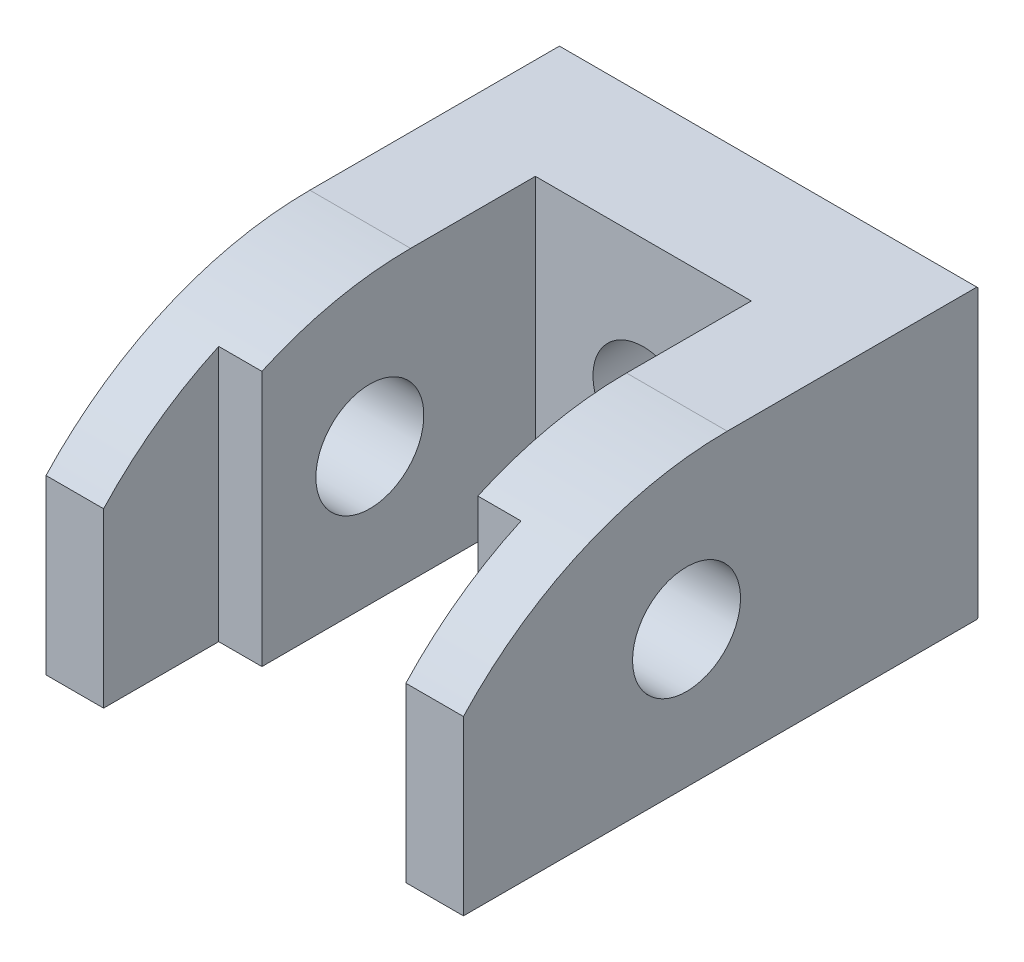
SolidWorks part; units mm, degrees
material "1060 Alloy"
ref_plane "Front Plane" through (0, 0, 0) normal (0, 0, 1) x (1, 0, 0)
ref_plane "Top Plane" through (0, 0, 0) normal (0, 1, 0) x (1, 0, 0)
ref_plane "Right Plane" through (0, 0, 0) normal (1, 0, 0) x (0, 0, -1)
sketch "Sketch2" plane through (0, 0, 0) normal (1, 0, 0) x (0, 0, -1)
  line L0 (0, 0) -> (0, 24)
  line L1 (0, 0) -> (65, 0)
  line L2 (65, 0) -> (80, 8.6603)
  line L3 (80, 8.6603) -> (80, 31.3397)
  line L4 (80, 31.3397) -> (65, 40)
  line L5 (65, 40) -> (36.6606, 40)
  arc A0 (36.6606, 40) -> (0, 24) centre (36.6606, -10) ccw
  circle A1 centre (31, 19) radius 7.5
  dimension "D8" = 50
  dimension "D9" = 15
  dimension "D10" = 19
  dimension "D11" = 31
  dimension "D1" = 24
  dimension "D2" = 65
  dimension "D3" = 15
  dimension "D4" = 30
  dimension "D5" = 30
  dimension "D6" = 40
  dimension "D7" = 15
extrude "Boss-Extrude1" add sketch "Sketch2" along normal blind 58
sketch "Sketch4" plane through (0, 0, 0) normal (0, -1, 0) x (1, 0, 0)
  line L1 (0, 0) -> (75.4894, 0) construction
  line L2 (0, 0) -> (0, -86.1611) construction
  line L3 (58, 0) -> (58, -65) construction
  line L4 (8, 0) -> (50, 0)
  line L5 (8, 0) -> (8, -16)
  line L6 (8, -16) -> (14, -16)
  line L7 (50, 0) -> (50, -16)
  line L8 (44, -16) -> (50, -16)
  line L10 (14, -16) -> (14, -54)
  line L11 (14, -54) -> (44, -54)
  line L12 (44, -16) -> (44, -54)
  line L13 (58, -65) -> (0, -65) construction
  dimension "D1" = 8
  dimension "D2" = 8
  dimension "D3" = 16
  dimension "D4" = 14
  dimension "D5" = 14
  dimension "D6" = 11
extrude "Cut-Extrude1" cut sketch "Sketch4" against normal through all
draft "Draft2" type of draft neutral plane draft angle 45 faces to draft 2 face at (29, 4.3301, -72.5) face at (29, 35.6699, -72.5) neutral plane through (58, 8.6603, -80) neutral plane normal (0, 0, -1) parameters "D1"=45
sketch "Sketch6" plane through (0, 0, -80) normal (0, 0, -1) x (-1, 0, 0)
  line L6 (-58, 31.3397) -> (-58, 40) construction
  line L7 (-58, 0) -> (0, 0) construction
  circle A0 centre (-29, 20) radius 7
  dimension "D2" = 14
  dimension "D3" = 29
  dimension "D4" = 20
extrude "Cut-Extrude6" cut sketch "Sketch6" against normal through all
sketch "Sketch11" plane through (58, 0, 0) normal (1, 0, 0) x (0, 0, -1)
  line L0 (71.3397, 40) -> (71.3397, 0)
  line L1 (71.3397, 0) -> (80, 8.6603)
  line L2 (80, 8.6603) -> (80, 31.3397)
  line L3 (80, 31.3397) -> (71.3397, 40)
sketch "Sketch12" plane through (0, 0, 0) normal (-1, 0, 0) x (0, 0, 1)
  line L0 (-71.3397, 40) -> (-71.3397, 0)
  line L1 (-71.3397, 0) -> (-80, 8.6603)
  line L2 (-80, 8.6603) -> (-80, 31.3397)
  line L3 (-80, 31.3397) -> (-71.3397, 40)
fillet "Chamfer9" radius 8.5 1 edges at (58, 20, -80) type face fillet profile chamfer first side face at (22, 20, -80) second side face at (58, 21.118, -48.2386)
fillet "Chamfer10" radius 8.5 1 edges at (0, 20, -80) type face fillet profile chamfer first side face at (0, 21.118, -48.2386) second side face at (22, 20, -80)
equation "\"a\"= 58"
equation "\"b\"= 40"
equation "\"c\"= 65"
